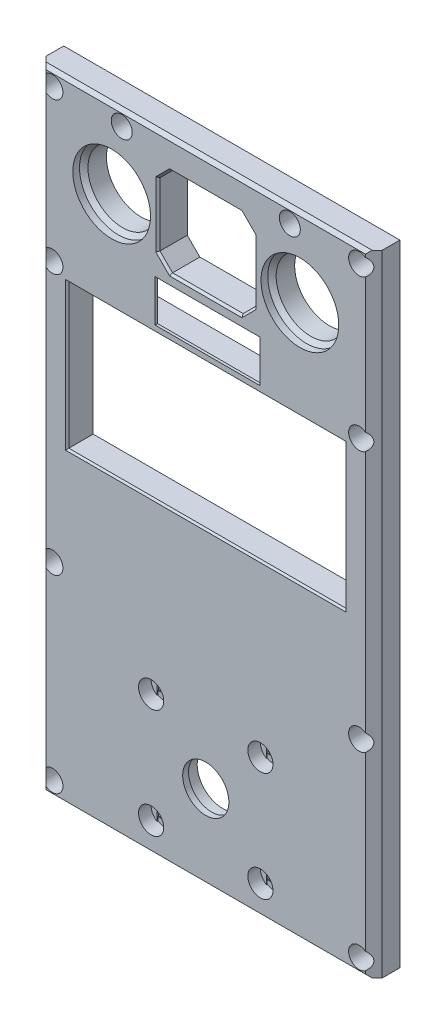
SolidWorks part; units mm, degrees
ref_plane "Front Plane" through (0, 0, 0) normal (0, 0, 1) x (1, 0, 0)
ref_plane "Top Plane" through (0, 0, 0) normal (0, 1, 0) x (1, 0, 0)
ref_plane "Right Plane" through (0, 0, 0) normal (1, 0, 0) x (0, 0, -1)
sketch "Sketch1" plane through (0, 0, 0) normal (0, 0, 1) x (1, 0, 0)
  line L1 (-40, -75) -> (40, -75)
  line L2 (-40, -75) -> (-40, 75)
  line L3 (-40, 75) -> (40, 75)
  line L4 (40, -75) -> (40, 75)
  line L5 (-40, -75) -> (40, 75) construction
  line L6 (-40, 75) -> (40, -75) construction
  line L7 (-33, -68) -> (33, -68)
  line L8 (-33, -68) -> (-33, 68)
  line L9 (-33, 68) -> (33, 68)
  line L10 (33, -68) -> (33, 68)
  line L11 (-33, -68) -> (33, 68) construction
  line L12 (-33, 68) -> (33, -68) construction
  point P0 (0, 0)
  point P6 (0, 0)
  dimension "D1" = 150
  dimension "D2" = 80
  dimension "D3" = 7
  dimension "D4" = 7
extrude "Boss-Extrude1" add sketch "Sketch1" along normal blind 7
sketch "Sketch2" plane through (0, 0, 7) normal (0, 0, 1) x (1, 0, 0)
  line L0 (33, -68) -> (33, 68) construction
  line L1 (-33, -68) -> (33, -68)
  line L2 (-33, -68) -> (-33, -32)
  line L3 (-33, -32) -> (33, -32)
  line L4 (33, -68) -> (33, -32)
  dimension "D1" = 36
extrude "Boss-Extrude2" add sketch "Sketch2" against normal up to surface (7 mm away) up to face at (0, 0, 0)
sketch "Sketch3" plane through (0, 0, 0) normal (0, 0, -1) x (-1, 0, 0)
  line L0 (0, -75) -> (0, -55) construction
  line L1 (40, -75) -> (-40, -75) construction
  circle A0 centre (0, -55) radius 5.5
  dimension "D1" = 11
  dimension "D2" = 20
extrude "Cut-Extrude1" cut sketch "Sketch3" against normal through all
sketch "Sketch4" plane through (0, 0, 0) normal (0, 0, -1) x (-1, 0, 0)
  circle A0 centre (0, -55) radius 6.05
  dimension "D1" = 12.1
extrude "Cut-Extrude2" cut sketch "Sketch4" against normal offset from surface (5.6 mm away) 1.4 up to face at (-5.5, -55, 7)
sketch "Sketch5" plane through (0, 0, 0) normal (0, 0, -1) x (-1, 0, 0)
  circle A0 centre (0, -55) radius 11.1
  dimension "D1" = 22.2
extrude "Cut-Extrude3" cut sketch "Sketch5" against normal offset from surface (3 mm away) 2.6 up to face at (-6.05, -55, 5.6)
sketch "Sketch6" plane through (0, 0, 0) normal (0, 0, -1) x (-1, 0, 0)
  line L1 (-13, -68) -> (13, -68) construction
  line L2 (-13, -68) -> (-13, -42) construction
  line L3 (-13, -42) -> (13, -42) construction
  line L4 (13, -68) -> (13, -42) construction
  line L5 (-13, -68) -> (13, -42) construction
  line L6 (-13, -42) -> (13, -68) construction
  circle A0 centre (-13, -42) radius 1.6
  circle A1 centre (13, -42) radius 1.6
  circle A2 centre (13, -68) radius 1.6
  circle A3 centre (-13, -68) radius 1.6
  point P0 (0, -55)
  dimension "D2" = 3.2
  dimension "D1" = 26
extrude "Cut-Extrude4" cut sketch "Sketch6" against normal through all
sketch "Sketch7" plane through (0, 0, 0) normal (0, 0, -1) x (-1, 0, 0)
  line L1 (-25, -74) -> (25, -74)
  line L2 (-25, -74) -> (-25, -36)
  line L3 (-25, -36) -> (25, -36)
  line L4 (25, -74) -> (25, -36)
  line L5 (-25, -74) -> (25, -36) construction
  line L6 (-25, -36) -> (25, -74) construction
  point P0 (0, -55)
  dimension "D1" = 50
  dimension "D2" = 38
extrude "Cut-Extrude5" cut sketch "Sketch7" against normal blind 1
sketch "Sketch8" plane through (0, 0, 7) normal (0, 0, 1) x (1, 0, 0)
  circle A0 centre (-13, -42) radius 3
  circle A1 centre (13, -42) radius 3
  circle A2 centre (13, -68) radius 3
  circle A3 centre (-13, -68) radius 3
  dimension "D1" = 6
extrude "Cut-Extrude6" cut sketch "Sketch8" against normal blind 3
sketch "Sketch9" plane through (0, 0, 7) normal (0, 0, 1) x (1, 0, 0)
  line L0 (-40, 75) -> (-40, -75) construction
  line L1 (-36.5, -71.5) -> (36.5, -71.5) construction
  line L2 (-36.5, -71.5) -> (-36.5, 71.5) construction
  line L3 (-36.5, 71.5) -> (36.5, 71.5) construction
  line L4 (36.5, -71.5) -> (36.5, 71.5) construction
  line L5 (-36.5, -71.5) -> (36.5, 71.5) construction
  line L6 (-36.5, 71.5) -> (36.5, -71.5) construction
  line L7 (40, 75) -> (-40, 75) construction
  circle A0 centre (-36.5, 71.5) radius 1.35
  circle A1 centre (36.5, 71.5) radius 1.35
  circle A2 centre (36.5, -71.5) radius 1.35
  circle A3 centre (-36.5, -71.5) radius 1.35
  circle A6 centre (-36.5, 35.5) radius 1.35
  circle A7 centre (-36.5, -26.5) radius 1.35
  circle A8 centre (36.5, -26.5) radius 1.35
  circle A9 centre (36.5, 35.5) radius 1.35
  point P0 (0, 0)
  dimension "D3" = 2.7
  dimension "D4" = 45
  dimension "D5" = 36
  dimension "D1" = 3.5
  dimension "D2" = 3.5
extrude "Cut-Extrude7" cut sketch "Sketch9" against normal through all
sketch "Sketch10" plane through (0, 0, 7) normal (0, 0, 1) x (1, 0, 0)
  circle A0 centre (-36.5, 71.5) radius 2.5
  circle A1 centre (36.5, 71.5) radius 2.5
  circle A2 centre (-36.5, 35.5) radius 2.5
  circle A3 centre (-36.5, -26.5) radius 2.5
  circle A4 centre (-36.5, -71.5) radius 2.5
  circle A5 centre (36.5, -71.5) radius 2.5
  circle A6 centre (36.5, 35.5) radius 2.5
  circle A7 centre (36.5, -26.5) radius 2.5
  dimension "D1" = 5
extrude "Cut-Extrude8" cut sketch "Sketch10" against normal blind 5
chamfer "Chamfer1" distance 2 angle 45 2 edges at (-40, 0, 7) (40, 0, 7)
sketch "Sketch11" plane through (0, 0, 7) normal (0, 0, 1) x (1, 0, 0)
  line L0 (33, -32) -> (33, 68) construction
  line L1 (-33, -32) -> (33, -32)
  line L2 (-33, -32) -> (-33, -1.5)
  line L3 (-33, -1.5) -> (33, -1.5)
  line L4 (33, -32) -> (33, -1.5)
  line L5 (-38, -75) -> (38, -75) construction
  dimension "D1" = 73.5
extrude "Boss-Extrude3" add sketch "Sketch11" against normal up to surface (7 mm away) up to face at (37.85, 71.5, 0)
sketch "Sketch12" plane through (0, 0, 2) normal (0, 0, 1) x (1, 0, 0)
  line L2 (-37.85, -73.6042) -> (-37.85, -69.3958)
  line L4 (-35.15, -73.6042) -> (-35.15, -69.3958)
  line L5 (-37.85, -73.6042) -> (-35.15, -69.3958) construction
  line L6 (-37.85, -69.3958) -> (-35.15, -73.6042) construction
  line L8 (-37.85, -28.6042) -> (-37.85, -24.3958)
  line L10 (-35.15, -28.6042) -> (-35.15, -24.3958)
  line L11 (-37.85, -28.6042) -> (-35.15, -24.3958) construction
  line L12 (-37.85, -24.3958) -> (-35.15, -28.6042) construction
  line L14 (-37.85, 33.3958) -> (-37.85, 37.6042)
  line L16 (-35.15, 33.3958) -> (-35.15, 37.6042)
  line L17 (-37.85, 33.3958) -> (-35.15, 37.6042) construction
  line L18 (-37.85, 37.6042) -> (-35.15, 33.3958) construction
  line L20 (-37.85, 69.3958) -> (-37.85, 73.6042)
  line L22 (-35.15, 69.3958) -> (-35.15, 73.6042)
  line L23 (-37.85, 69.3958) -> (-35.15, 73.6042) construction
  line L24 (-37.85, 73.6042) -> (-35.15, 69.3958) construction
  arc A0 (-38, -73.5) -> (-38, -69.5) centre (-36.5, -71.5) ccw construction
  circle A1 centre (-36.5, -26.5) radius 2.5 construction
  circle A2 centre (-36.5, 35.5) radius 2.5 construction
  arc A3 (-38, 69.5) -> (-38, 73.5) centre (-36.5, 71.5) ccw construction
  circle A4 centre (-36.5, 71.5) radius 1.35 construction
  circle A5 centre (-36.5, 71.5) radius 2.5 construction
  arc A6 (-35.15, 73.6042) -> (-37.85, 73.6042) centre (-36.5, 71.5) ccw
  arc A7 (-37.85, 69.3958) -> (-35.15, 69.3958) centre (-36.5, 71.5) ccw
  circle A8 centre (-36.5, 35.5) radius 1.35 construction
  arc A9 (-37.85, 33.3958) -> (-35.15, 33.3958) centre (-36.5, 35.5) ccw
  arc A10 (-35.15, 37.6042) -> (-37.85, 37.6042) centre (-36.5, 35.5) ccw
  circle A11 centre (-36.5, -26.5) radius 1.35 construction
  arc A12 (-37.85, -28.6042) -> (-35.15, -28.6042) centre (-36.5, -26.5) ccw
  arc A13 (-35.15, -24.3958) -> (-37.85, -24.3958) centre (-36.5, -26.5) ccw
  circle A14 centre (-36.5, -71.5) radius 1.35 construction
  arc A16 (-37.85, -73.6042) -> (-35.15, -73.6042) centre (-36.5, -71.5) ccw
  arc A18 (-35.15, -69.3958) -> (-37.85, -69.3958) centre (-36.5, -71.5) ccw
  point P0 (-36.5, -71.5)
  point P9 (-36.5, -26.5)
  point P17 (-36.5, 35.5)
  point P25 (-36.5, 71.5)
extrude "Cut-Extrude9" cut sketch "Sketch12" against normal blind 0.2
sketch "Sketch13" plane through (0, 0, 1.8) normal (0, 0, 1) x (1, 0, 0)
  line L0 (-35.15, -71.5) -> (-35.15, -69.3958) construction
  line L1 (-37.85, -72.85) -> (-35.15, -72.85)
  line L2 (-37.85, -72.85) -> (-37.85, -70.15)
  line L3 (-37.85, -70.15) -> (-35.15, -70.15)
  line L4 (-35.15, -72.85) -> (-35.15, -70.15)
  line L5 (-37.85, -72.85) -> (-35.15, -70.15) construction
  line L6 (-37.85, -70.15) -> (-35.15, -72.85) construction
  line L7 (-35.15, -26.5) -> (-35.15, -24.3958) construction
  line L8 (-37.85, -27.85) -> (-35.15, -27.85)
  line L9 (-37.85, -27.85) -> (-37.85, -25.15)
  line L10 (-37.85, -25.15) -> (-35.15, -25.15)
  line L11 (-35.15, -27.85) -> (-35.15, -25.15)
  line L12 (-37.85, -27.85) -> (-35.15, -25.15) construction
  line L13 (-37.85, -25.15) -> (-35.15, -27.85) construction
  line L14 (-35.15, 33.3958) -> (-35.15, 37.6042) construction
  line L15 (-37.85, 34.15) -> (-35.15, 34.15)
  line L16 (-37.85, 34.15) -> (-37.85, 36.85)
  line L17 (-37.85, 36.85) -> (-35.15, 36.85)
  line L18 (-35.15, 34.15) -> (-35.15, 36.85)
  line L19 (-37.85, 34.15) -> (-35.15, 36.85) construction
  line L20 (-37.85, 36.85) -> (-35.15, 34.15) construction
  line L21 (-35.15, 69.3958) -> (-35.15, 73.6042) construction
  line L22 (-37.85, 70.15) -> (-35.15, 70.15)
  line L23 (-37.85, 70.15) -> (-37.85, 72.85)
  line L24 (-37.85, 72.85) -> (-35.15, 72.85)
  line L25 (-35.15, 70.15) -> (-35.15, 72.85)
  line L26 (-37.85, 70.15) -> (-35.15, 72.85) construction
  line L27 (-37.85, 72.85) -> (-35.15, 70.15) construction
  arc A0 (-35.15, -71.5) -> (-37.85, -71.5) centre (-36.5, -71.5) ccw construction
  arc A1 (-35.15, -26.5) -> (-37.85, -26.5) centre (-36.5, -26.5) ccw construction
  arc A2 (-35.15, 35.5) -> (-37.85, 35.5) centre (-36.5, 35.5) ccw construction
  arc A3 (-35.15, 71.5) -> (-37.85, 71.5) centre (-36.5, 71.5) ccw construction
  point P0 (-36.5, -71.5)
  point P11 (-36.5, -26.5)
  point P22 (-36.5, 35.5)
  point P33 (-36.5, 71.5)
extrude "Cut-Extrude10" cut sketch "Sketch13" against normal blind 0.2
sketch "Sketch14" plane through (0, 0, 4) normal (0, 0, 1) x (1, 0, 0)
  line L2 (-14.6, -44.5377) -> (-14.6, -39.4623)
  line L4 (-11.4, -44.5377) -> (-11.4, -39.4623)
  line L5 (-14.6, -44.5377) -> (-11.4, -39.4623) construction
  line L6 (-14.6, -39.4623) -> (-11.4, -44.5377) construction
  line L8 (-14.6, -70.5377) -> (-14.6, -65.4623)
  line L10 (-11.4, -70.5377) -> (-11.4, -65.4623)
  line L11 (-14.6, -70.5377) -> (-11.4, -65.4623) construction
  line L12 (-14.6, -65.4623) -> (-11.4, -70.5377) construction
  circle A0 centre (-13, -42) radius 3 construction
  circle A1 centre (-13, -68) radius 3 construction
  circle A2 centre (-13, -42) radius 3 construction
  arc A3 (-14.6, -44.5377) -> (-11.4, -44.5377) centre (-13, -42) ccw
  arc A4 (-14.6, -70.5377) -> (-11.4, -70.5377) centre (-13, -68) ccw
  circle A5 centre (-13, -42) radius 1.6 construction
  circle A6 centre (-13, -68) radius 1.6 construction
  arc A7 (-11.4, -39.4623) -> (-14.6, -39.4623) centre (-13, -42) ccw
  arc A8 (-11.4, -65.4623) -> (-14.6, -65.4623) centre (-13, -68) ccw
  point P0 (-13, -42)
  point P8 (-13, -68)
extrude "Cut-Extrude11" cut sketch "Sketch14" against normal blind 0.2
sketch "Sketch15" plane through (0, 0, 3.8) normal (0, 0, 1) x (1, 0, 0)
  line L0 (-11.4, -42) -> (-11.4, -39.4623) construction
  line L1 (-14.6, -43.6) -> (-11.4, -43.6)
  line L2 (-14.6, -43.6) -> (-14.6, -40.4)
  line L3 (-14.6, -40.4) -> (-11.4, -40.4)
  line L4 (-11.4, -43.6) -> (-11.4, -40.4)
  line L5 (-14.6, -43.6) -> (-11.4, -40.4) construction
  line L6 (-14.6, -40.4) -> (-11.4, -43.6) construction
  line L7 (-11.4, -68) -> (-11.4, -65.4623) construction
  line L8 (-14.6, -69.6) -> (-11.4, -69.6)
  line L9 (-14.6, -69.6) -> (-14.6, -66.4)
  line L10 (-14.6, -66.4) -> (-11.4, -66.4)
  line L11 (-11.4, -69.6) -> (-11.4, -66.4)
  line L12 (-14.6, -69.6) -> (-11.4, -66.4) construction
  line L13 (-14.6, -66.4) -> (-11.4, -69.6) construction
  arc A0 (-11.4, -68) -> (-14.6, -68) centre (-13, -68) ccw construction
  arc A1 (-14.6, -42) -> (-11.4, -42) centre (-13, -42) ccw construction
  point P0 (-13, -42)
  point P8 (-13, -68)
extrude "Cut-Extrude12" cut sketch "Sketch15" against normal blind 0.2
mirror "Mirror1" about plane through (0, 0, 0) normal (1, 0, 0) of "Cut-Extrude10", "Cut-Extrude11", "Cut-Extrude12", "Cut-Extrude9"
chamfer "Chamfer2" distance 0.4 angle 45 4 edges at (33, 33.25, 7) (0, 68, 7) (0, -1.5, 7) (-33, 33.25, 7)
chamfer "Chamfer3" distance 0.8 angle 45 4 edges at (-40, 0, 0) (40, 0, 0) (0, -75, 7) (0, 75, 7)
sketch "Sketch16" plane through (0, 0, 0) normal (1, 0, 0) x (0, 0, -1)
  line L0 (0, -4) -> (0, -15.4)
  line L1 (0, 75) -> (0, -75) construction
  line L2 (0, -15.4) -> (3.2, -12.2)
  line L3 (3.2, -12.2) -> (3.2, -7.2)
  line L4 (3.2, -7.2) -> (0, -4)
  line L5 (0, -15.4) -> (0, -19.4) construction
  line L6 (0.6, -7.7) -> (2.6, -7.7)
  line L7 (0.6, -7.7) -> (0.6, -11.7)
  line L8 (0.6, -11.7) -> (2.6, -11.7)
  line L9 (2.6, -7.7) -> (2.6, -11.7)
  line L10 (-1.046, -17.4) -> (12.8392, -17.4) construction
  line L11 (2.6, -27.1) -> (2.6, -23.1)
  line L12 (0.6, -23.1) -> (2.6, -23.1)
  line L13 (0.6, -27.1) -> (0.6, -23.1)
  line L14 (0.6, -27.1) -> (2.6, -27.1)
  line L15 (3.2, -27.6) -> (0, -30.8)
  line L16 (3.2, -22.6) -> (3.2, -27.6)
  line L17 (0, -19.4) -> (3.2, -22.6)
  line L18 (0, -30.8) -> (0, -19.4)
  point P10 (2.6, -9.7)
  point P11 (3.2, -9.7)
  point P24 (0, -17.4)
  dimension "D1" = 5
  dimension "D2" = 2
  dimension "D3" = 0.6
  dimension "D4" = 0.6
  dimension "D5" = 45
  dimension "D6" = 4
  dimension "D7" = 4
  dimension "D8" = 4
extrude "Boss-Extrude4" add sketch "Sketch16" along normal mid plane 2
pattern_linear "LPattern1" count 2 spacing 20 along (1, 0, 0) count 2 spacing 20 along (-1, 0, 0) of "Boss-Extrude4"
sketch "Sketch17" plane through (0, 0, 0) normal (0, 0, -1) x (-1, 0, 0)
  line L0 (-20, 71.5) -> (20, 71.5) construction
  line L1 (-39.2, 75) -> (39.2, 75) construction
  circle A0 centre (-36.5, 71.5) radius 1.35 construction
  circle A1 centre (-36.5, 71.5) radius 1.35 construction
  circle A2 centre (-20, 71.5) radius 1.35
  circle A3 centre (20, 71.5) radius 1.35
  point P3 (0, 71.5)
  point P6 (0, 75)
  dimension "D1" = 40
extrude "Cut-Extrude13" cut sketch "Sketch17" against normal through all
sketch "Sketch18" plane through (0, 0, 7) normal (0, 0, 1) x (1, 0, 0)
  circle A0 centre (-20, 71.5) radius 2.5
  circle A1 centre (20, 71.5) radius 2.5
  arc A2 (-38, 69.5) -> (-38, 73.5) centre (-36.5, 71.5) ccw construction
extrude "Cut-Extrude14" cut sketch "Sketch18" against normal up to surface (5 mm away) up to face at (38.425, 71.5, 2)
sketch "Sketch19" plane through (0, 0, 2) normal (0, 0, 1) x (1, 0, 0)
  line L2 (-21.35, 69.3958) -> (-21.35, 73.6042)
  line L4 (-18.65, 69.3958) -> (-18.65, 73.6042)
  line L5 (-21.35, 69.3958) -> (-18.65, 73.6042) construction
  line L6 (-21.35, 73.6042) -> (-18.65, 69.3958) construction
  line L8 (18.65, 69.3958) -> (18.65, 73.6042)
  line L10 (21.35, 69.3958) -> (21.35, 73.6042)
  line L11 (18.65, 69.3958) -> (21.35, 73.6042) construction
  line L12 (18.65, 73.6042) -> (21.35, 69.3958) construction
  circle A0 centre (-20, 71.5) radius 2.5 construction
  circle A1 centre (20, 71.5) radius 2.5 construction
  circle A2 centre (20, 71.5) radius 1.35 construction
  circle A3 centre (-20, 71.5) radius 1.35 construction
  circle A4 centre (-20, 71.5) radius 2.5 construction
  arc A5 (18.65, 69.3958) -> (21.35, 69.3958) centre (20, 71.5) ccw
  arc A6 (-18.65, 73.6042) -> (-21.35, 73.6042) centre (-20, 71.5) ccw
  arc A7 (21.35, 73.6042) -> (18.65, 73.6042) centre (20, 71.5) ccw
  arc A8 (-21.35, 69.3958) -> (-18.65, 69.3958) centre (-20, 71.5) ccw
  point P0 (-20, 71.5)
  point P8 (20, 71.5)
extrude "Cut-Extrude15" cut sketch "Sketch19" against normal blind 0.2
sketch "Sketch20" plane through (0, 0, 1.8) normal (0, 0, 1) x (1, 0, 0)
  line L0 (-18.65, 69.3958) -> (-18.65, 73.6042) construction
  line L1 (-21.35, 70.15) -> (-18.65, 70.15)
  line L2 (-21.35, 70.15) -> (-21.35, 72.85)
  line L3 (-21.35, 72.85) -> (-18.65, 72.85)
  line L4 (-18.65, 70.15) -> (-18.65, 72.85)
  line L5 (-21.35, 70.15) -> (-18.65, 72.85) construction
  line L6 (-21.35, 72.85) -> (-18.65, 70.15) construction
  line L7 (21.35, 71.5) -> (21.35, 73.6042) construction
  line L8 (18.65, 70.15) -> (21.35, 70.15)
  line L9 (18.65, 70.15) -> (18.65, 72.85)
  line L10 (18.65, 72.85) -> (21.35, 72.85)
  line L11 (21.35, 70.15) -> (21.35, 72.85)
  line L12 (18.65, 70.15) -> (21.35, 72.85) construction
  line L13 (18.65, 72.85) -> (21.35, 70.15) construction
  arc A0 (18.65, 71.5) -> (21.35, 71.5) centre (20, 71.5) ccw construction
  point P0 (-20, 71.5)
  point P8 (20, 71.5)
extrude "Cut-Extrude16" cut sketch "Sketch20" against normal blind 0.2
sketch "Skizze4" plane through (0, 0, 0) normal (0, 0, -1) x (-1, 0, 0)
  line L1 (21, -4) -> (-21, -4)
  line L2 (21, -4) -> (21, -30.8)
  line L3 (21, -30.8) -> (-21, -30.8)
  line L4 (-21, -4) -> (-21, -30.8)
extrude "Schnitt-Linear austragen1" cut sketch "Skizze4" along normal up to surface (3.2 mm away) up to face at (-20, -9.7, -3.2)
sketch "Skizze6" plane through (0, 0, 7) normal (0, 0, 1) x (1, 0, 0)
  line L0 (11.4, 68.4) -> (33.4, 46.4) construction
  line L1 (33.4, 68.4) -> (11.4, 68.4)
  line L2 (33.4, 68.4) -> (33.4, 46.4)
  line L3 (33.4, 46.4) -> (11.4, 46.4)
  line L4 (11.4, 68.4) -> (11.4, 46.4)
  line L5 (22.4, 68.4) -> (22.4, 46.4) construction
  circle A0 centre (22.4, 56.4) radius 8.25
  point P10 (22.4, 57.4)
  dimension "D1" = 16.5
  dimension "D2" = 22
  dimension "D3" = 22
  dimension "D4" = 1
extrude "Aufsatz-Linear austragen1" add sketch "Skizze6" against normal up to surface (7 mm away) up to face at (18.65, 71.5, 0)
sketch "Skizze7" plane through (0, 0, 7) normal (0, 0, 1) x (1, 0, 0)
  circle A0 centre (22.4, 56.4) radius 9.25
  dimension "D1" = 18.5
extrude "Schnitt-Linear austragen2" cut sketch "Skizze7" against normal blind 1.6
chamfer "Fase6" distance 0.5 angle 45 2 edges at (11.4, 57.4, 7) (22.4, 46.4, 7)
chamfer "Fase7" distance 4 angle 45 1 edges at (11.4, 46.4, 3.25)
chamfer "Fase8" distance 1 angle 45 1 edges at (30.65, 56.4, 5.4)
mirror "Mirror2" about plane through (0, 0, 0) normal (1, 0, 0) of "Fase6", "Schnitt-Linear austragen2", "Fase8", "Aufsatz-Linear austragen1", "Fase7"
sketch "Sketch21" plane through (0, 0, 7) normal (0, 0, 1) x (1, 0, 0)
  line L0 (33.4, 46.9) -> (33.4, -1.9) construction
  line L1 (-33.4, 46.9) -> (-14.9, 46.9)
  line L2 (-33.4, 46.9) -> (-33.4, 32.9)
  line L3 (-33.4, 32.9) -> (33.4, 32.9)
  line L4 (33.4, 46.9) -> (33.4, 32.9)
  line L5 (-14.9, 46.9) -> (-11.4, 50.4)
  line L6 (-11.4, 50.4) -> (-11.4, 46.9)
  line L7 (11.4, 50.4) -> (14.9, 46.9)
  line L8 (11.4, 50.4) -> (11.4, 46.9)
  line L9 (-11.4, 46.9) -> (11.4, 46.9)
  line L10 (14.9, 46.9) -> (33.4, 46.9)
  dimension "D1" = 14
extrude "Boss-Extrude5" add sketch "Sketch21" against normal up to surface (7 mm away) up to face at (0, 41.94, 0)
chamfer "Chamfer4" distance 0.5 angle 45 3 edges at (11.4, 48.65, 7) (-11.4, 48.65, 7) (0, 46.9, 7)
sketch "Sketch22" plane through (0, 0, 0) normal (0, 0, -1) x (-1, 0, 0)
  line L0 (0, 46.9) -> (0, 32.9) construction
  line L1 (-11.4, 46.9) -> (11.4, 46.9) construction
  line L2 (33, 32.9) -> (-33, 32.9) construction
  line L4 (-18.95, 33.75) -> (18.95, 33.75)
  line L5 (-18.95, 33.75) -> (-18.95, 46.05)
  line L6 (-18.95, 46.05) -> (18.95, 46.05)
  line L7 (18.95, 33.75) -> (18.95, 46.05)
  line L8 (-18.95, 33.75) -> (18.95, 46.05) construction
  line L9 (-18.95, 46.05) -> (18.95, 33.75) construction
  point P6 (0, 39.9)
  dimension "D1" = 37.9
  dimension "D2" = 12.3
extrude "Cut-Extrude17" cut sketch "Sketch22" against normal offset from surface (6.4 mm away) 0.6 up to face at (0, 15.5, 7)
sketch "Sketch23" plane through (0, 0, 6.4) normal (0, 0, -1) x (-1, 0, 0)
  line L0 (-18.95, 46.05) -> (-18.95, 33.75) construction
  line L1 (-12.95, 34.55) -> (12.05, 34.55)
  line L2 (-12.95, 34.55) -> (-12.95, 44.55)
  line L3 (-12.95, 44.55) -> (12.05, 44.55)
  line L4 (12.05, 34.55) -> (12.05, 44.55)
  line L5 (-12.95, 34.55) -> (12.05, 44.55) construction
  line L6 (-12.95, 44.55) -> (12.05, 34.55) construction
  line L7 (-18.95, 46.05) -> (18.95, 46.05) construction
  point P0 (-0.45, 39.55)
  dimension "D1" = 25
  dimension "D2" = 10
  dimension "D3" = 6
  dimension "D4" = 1.5
extrude "Cut-Extrude18" cut sketch "Sketch23" against normal through all
chamfer "Chamfer5" distance 0.4 angle 45 1 edges at (0, 32.9, 7)
sketch "Sketch24" plane through (0, 0, 7) normal (0, 0, 1) x (1, 0, 0)
  line L1 (-11.9, 68.4) -> (11.9, 68.4)
  line L2 (-11.9, 68.4) -> (-11.9, 46.4)
  line L3 (-11.9, 46.4) -> (11.9, 46.4)
  line L4 (11.9, 68.4) -> (11.9, 46.4)
  line L5 (-11.4, 68) -> (11.4, 68)
  line L6 (-11.4, 68) -> (-11.4, 46.9)
  line L7 (-11.4, 46.9) -> (11.4, 46.9)
  line L8 (11.4, 68) -> (11.4, 46.9)
extrude "Boss-Extrude6" add sketch "Sketch24" against normal up to vertex (0.5 mm away) up to point (11.4, 46.9, 6.5)
chamfer "Chamfer7" distance 3 angle 45 4 edges at (11.4, 46.9, 3.5) (11.4, 68, 3.5) (-11.4, 68, 3.5) (-11.4, 46.9, 3.5)
chamfer "Chamfer8" distance 0.5 angle 45 8 edges at (-9.9, 48.4, 7) (0, 46.9, 7) (9.9, 48.4, 7) (11.4, 57.45, 7) (9.9, 66.5, 7) (0, 68, 7) (-9.9, 66.5, 7) (-11.4, 57.45, 7)
chamfer "Chamfer9" distance 0.8 angle 45 6 edges at (-33, 15.7, 0) (0, 32.9, 0) (33, 15.7, 0) (0, -1.5, 0) (0, -75, 0) (0, 75, 0)
sketch "Sketch25" plane through (0, 0, 0) normal (0, 0, -1) x (-1, 0, 0)
  line L0 (-4, -11) -> (4, -11) construction
  line L1 (-6.75, -14) -> (6.75, -14)
  line L2 (-6.75, -14) -> (-6.75, -8)
  line L3 (-6.75, -8) -> (6.75, -8)
  line L4 (6.75, -14) -> (6.75, -8)
  line L5 (-6.75, -14) -> (6.75, -8) construction
  line L6 (-6.75, -8) -> (6.75, -14) construction
  circle A0 centre (-4, -11) radius 1.65
  circle A1 centre (4, -11) radius 1.65
  point P0 (0, -11)
  point P8 (0, -11)
  dimension "D2" = 3.3
  dimension "D1" = 8
  dimension "D3" = 13.5
  dimension "D4" = 6
  dimension "D5" = 11
extrude "Boss-Extrude7" add sketch "Sketch25" along normal blind 1
sketch "Sketch27" plane through (0, 0, -1) normal (0, 0, -1) x (-1, 0, 0)
  circle A0 centre (4, -11) radius 1.65 construction
  circle A1 centre (-4, -11) radius 1.65 construction
  circle A2 centre (4, -11) radius 1.65
  circle A3 centre (-4, -11) radius 1.65
extrude "Cut-Extrude19" cut sketch "Sketch27" against normal blind 6
